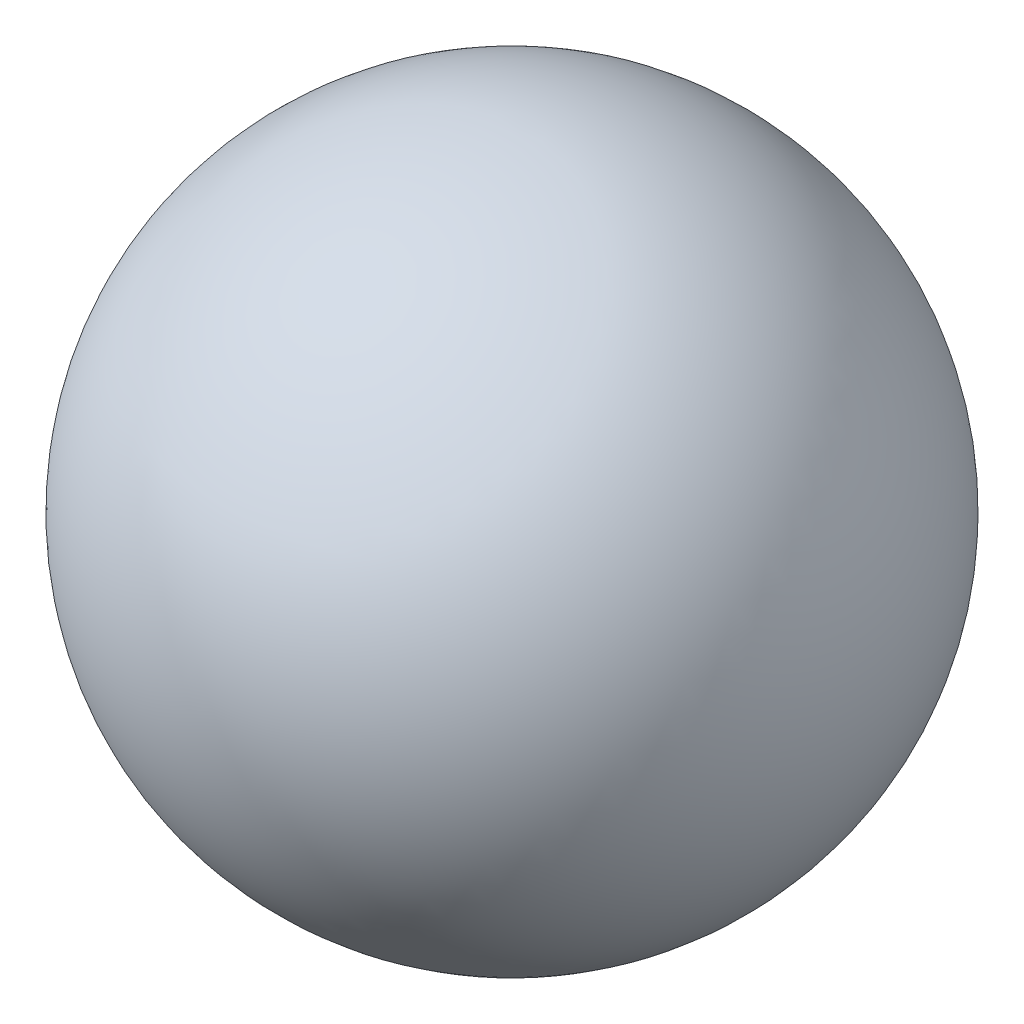
SolidWorks part; units mm, degrees
ref_plane "Front Plane" through (0, 0, 0) normal (0, 0, 1) x (1, 0, 0)
ref_plane "Top Plane" through (0, 0, 0) normal (0, 1, 0) x (1, 0, 0)
ref_plane "Right Plane" through (0, 0, 0) normal (1, 0, 0) x (0, 0, -1)
sketch "Sketch1" plane through (0, 0, 0) normal (0, 0, 1) x (1, 0, 0)
  line L0 (0, 0) -> (0, 60) construction
  line L1 (0, 0) -> (0, 60)
  arc A0 (0, 0) -> (0, 60) centre (0, 30) ccw
  dimension "D1" = 60
revolve "Revolve1" add sketch "Sketch1" angle 360 about L0
sketch "Sketch2" plane through (0, 0, 0) normal (0, 0, 1) x (1, 0, 0)
  line L0 (0, 30) -> (0, 0) construction
  circle A0 centre (0, 30) radius 6.325
  dimension "D2" = 12.65
  dimension "D1" = 30
extrude "Cut-Extrude1" cut sketch "Sketch2" against normal blind 35
sketch "Sketch3" plane through (0, 0, 0) normal (0, 1, 0) x (1, 0, 0)
  circle A0 centre (0, 0) radius 5
  dimension "D1" = 10
extrude "Cut-Extrude2" cut sketch "Sketch3" along normal blind 30
fillet "Fillet1" radius 5 1 edges at (0, 30, 0)
